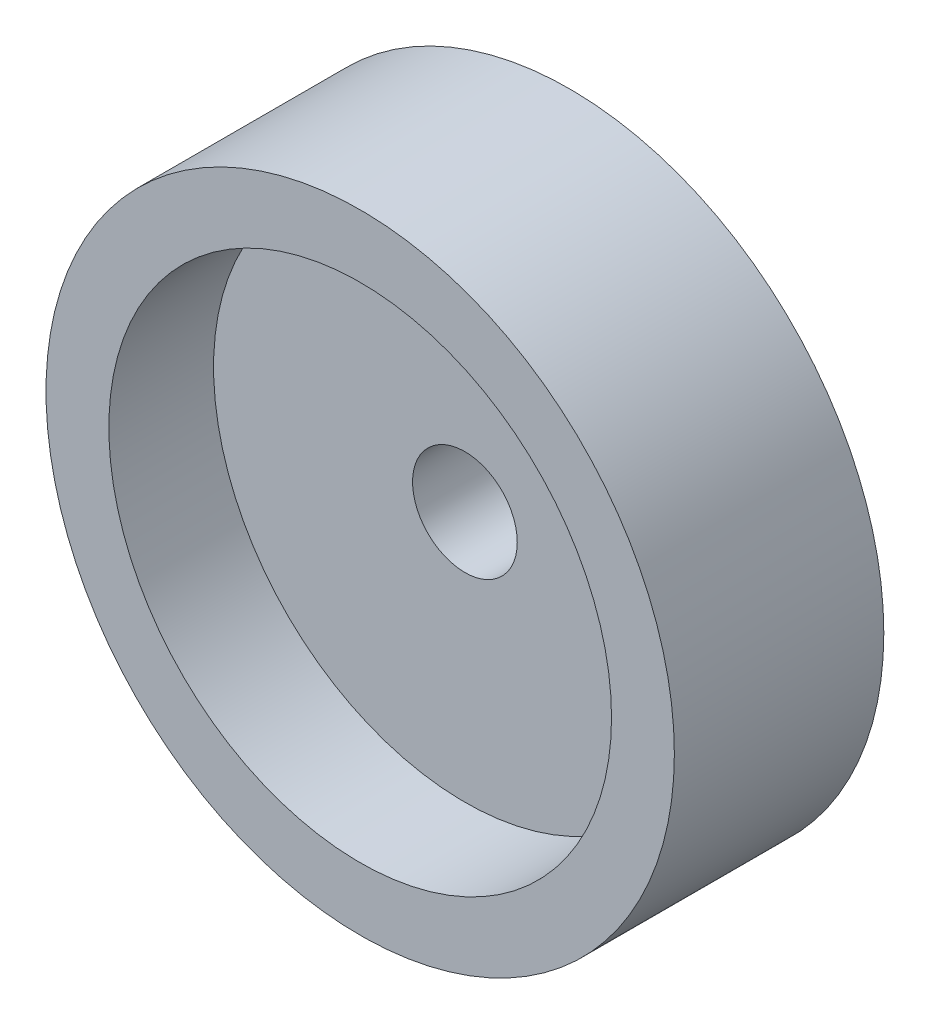
SolidWorks part; units mm, degrees
ref_plane "Front Plane" through (0, 0, 0) normal (0, 0, 1) x (1, 0, 0)
ref_plane "Top Plane" through (0, 0, 0) normal (0, 1, 0) x (1, 0, 0)
ref_plane "Right Plane" through (0, 0, 0) normal (1, 0, 0) x (0, 0, -1)
sketch "Sketch2" plane through (0, 0, 0) normal (0, 0, 1) x (1, 0, 0)
  circle A0 centre (0, 0) radius 1.5875
  circle A1 centre (0, 0) radius 7.62
  circle A2 centre (0, 0) radius 9.525
  dimension "D1" = 3.175
  dimension "D2" = 15.24
  dimension "D3" = 19.05
extrude "Boss-Extrude1" add sketch "Sketch2" along normal blind 3.175 contours A1 A0 region at (-7.4045, 0, 0)
extrude "Boss-Extrude3" add sketch "Sketch2<4>" along normal blind 6.35 contours A2 A1 region at (-9.2556, 0, 0)
sketch "Sketch2<4>" plane through (0, 0, 0) normal (0, 0, 1) x (1, 0, 0) same geometry as "Sketch2"
